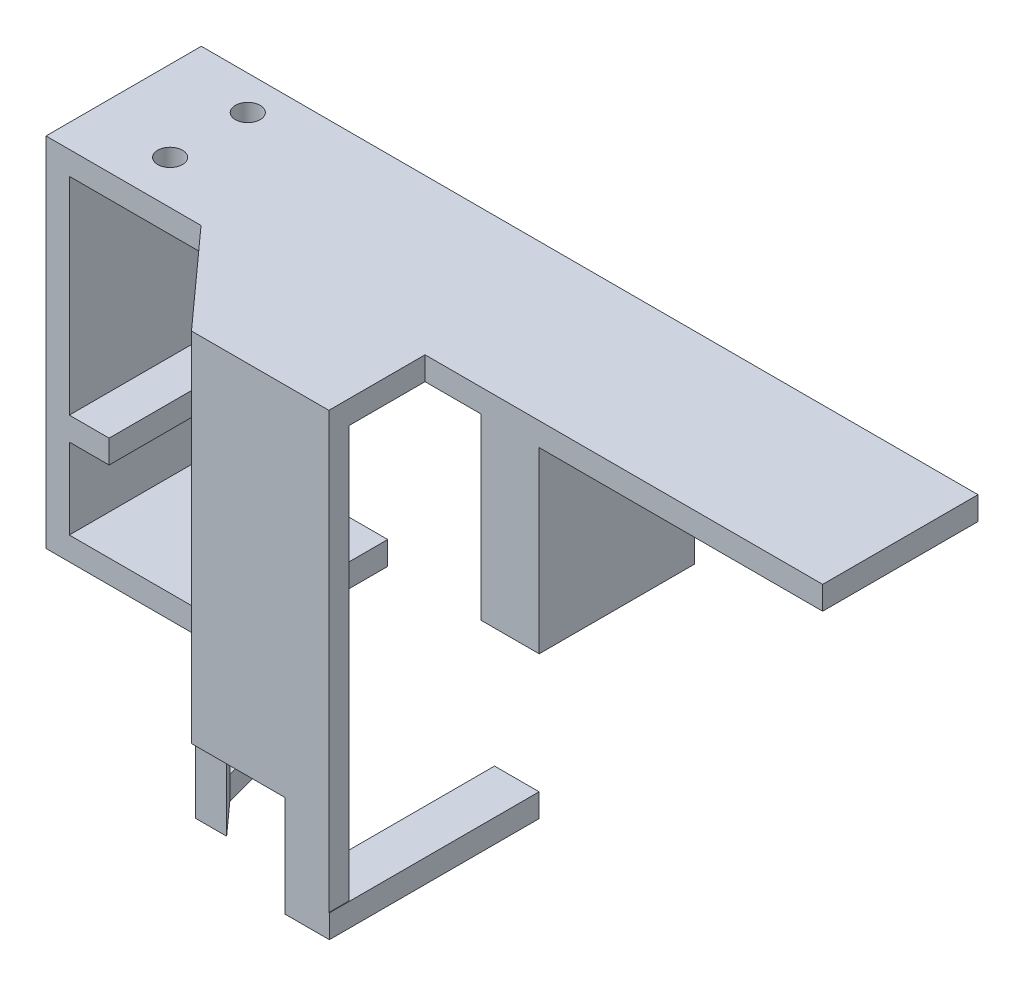
SolidWorks part; units mm, degrees
ref_plane "Front" through (0, 0, 0) normal (0, 0, 1) x (1, 0, 0)
ref_plane "Top" through (0, 0, 0) normal (0, 1, 0) x (1, 0, 0)
ref_plane "Right" through (0, 0, 0) normal (1, 0, 0) x (0, 0, -1)
sketch "Sketch1" plane through (0, 0, 0) normal (0, 1, 0) x (1, 0, 0)
  line L1 (0, 0) -> (100, 0)
  line L2 (0, 0) -> (0, 20)
  line L3 (0, 20) -> (100, 20)
  line L4 (100, 0) -> (100, 20)
  dimension "D1" = 100
  dimension "D2" = 20
extrude "Boss-Extrude1" add sketch "Sketch1" along normal blind 3
sketch "Sketch4" plane through (0, 0, -20) normal (0, 0, -1) x (-1, 0, 0)
  line L1 (0, 0) -> (-3, 0)
  line L2 (0, 0) -> (0, -43)
  line L3 (0, -43) -> (-3, -43)
  line L4 (-3, 0) -> (-3, -43)
  line L6 (-3, -24) -> (-3, -26.6921)
  line M5 (-100, 0) -> (0, 0)
  dimension "D1" = 43
  dimension "D4" = 3
extrude "Boss-Extrude3" add sketch "Sketch4" against normal blind 20 contours L4 L3 L2 M5 | L4 region at (1.5, -21.5, -20)
sketch "Sketch8" plane through (0, 0, -20) normal (0, 0, -1) x (-1, 0, 0)
  line L0 (0, 3) -> (0, -43) construction
  line L1 (-24, -40) -> (0, -40)
  line L2 (-24, -40) -> (-24, -43)
  line L3 (-24, -43) -> (0, -43)
  line L4 (0, -40) -> (0, -43)
  line L5 (0, -43) -> (-3, -43) construction
  dimension "D1" = 24
  dimension "D2" = 0
  dimension "D3" = 0
  dimension "D4" = 3
extrude "Boss-Extrude6" add sketch "Sketch8" against normal blind 20
sketch "Sketch10" plane through (0, 0, 0) normal (0, 0, 1) x (1, 0, 0)
  line L0 (3, -40) -> (24, -40) construction
  line L1 (2.1265, -29.63) -> (8.1265, -29.63)
  line L2 (2.1265, -29.63) -> (2.1265, -26.63)
  line L3 (2.1265, -26.63) -> (8.1265, -26.63)
  line L4 (8.1265, -29.63) -> (8.1265, -26.63)
  dimension "D1" = 10.37
  dimension "D2" = 3
  dimension "D3" = 6
extrude "Boss-Extrude9" add sketch "Sketch10" against normal blind 20
sketch "Sketch11" plane through (0, -43, 0) normal (0, -1, 0) x (1, 0, 0)
  circle A0 centre (20.8527, -10.1658) radius 1.5
sketch "Sketch12" plane through (0, -43, 0) normal (0, -1, 0) x (-1, 0, 0)
  line L0 (0, 0) -> (0, 20) construction
  line L1 (0, 0) -> (-24, 0) construction
  circle A0 centre (-10.38, 5.6) radius 1.6
  circle A1 centre (-10.38, 15.6) radius 1.6
  dimension "D2" = 5.6
  dimension "D3" = 10
  dimension "D1" = 10.38
extrude "Cut-Extrude1" cut sketch "Sketch12" against normal blind 80
extrude "Cut-Extrude2" cut sketch "Sketch11" against normal blind 20 contours A0
sketch "Sketch13" plane through (0, -43, 0) normal (0, -1, 0) x (1, 0, 0)
  line L1 (5.0707, -18.7755) -> (13.032, -18.7755)
  line L2 (5.0707, -18.7755) -> (5.0707, -3.4745)
  line L3 (5.0707, -3.4745) -> (13.032, -3.4745)
  line L4 (13.032, -18.7755) -> (13.032, -3.4745)
extrude "Boss-Extrude10" add sketch "Sketch13" against normal blind 3
sketch "Sketch14" plane through (0, 0, 0) normal (0, -1, 0) x (-1, 0, 0)
  line L0 (-3, 0) -> (-100, 0) construction
  line L1 (-63.4991, 0) -> (-56.0346, 0)
  line L2 (-63.4991, 0) -> (-63.4991, 20)
  line L3 (-63.4991, 20) -> (-56.0346, 20)
  line L4 (-56.0346, 0) -> (-56.0346, 20)
  line L5 (-100, 20) -> (-3, 20) construction
extrude "Boss-Extrude13" add sketch "Sketch14" along normal blind 23
sketch "Sketch18" plane through (0, -43, 0) normal (0, -1, 0) x (1, 0, 0)
  line L0 (24, 0) -> (32.8053, 9.7793)
  line L1 (32.8053, 9.7793) -> (48.8053, 9.7793)
  line L2 (48.8053, 9.7793) -> (48.8053, 12.3849)
  line L3 (48.8053, 12.3849) -> (31.1145, 12.3849)
  line L4 (31.1145, 12.3849) -> (19.9631, 0)
  line L5 (0, 0) -> (24, 0) construction
  line L6 (19.9631, 0) -> (24, 0)
  dimension "D1" = 132
  dimension "D2" = 3
  dimension "D3" = 16
extrude "Boss-Extrude15" add sketch "Sketch18" against normal blind 46
sketch "Sketch19" plane through (0, 3, 0) normal (0, 1, 0) x (1, 0, 0)
  line L0 (24, 0) -> (32.8053, -9.7793)
  line L1 (32.8053, -9.7793) -> (48.8053, -9.7793)
  line L2 (48.8053, -9.7793) -> (48.8053, 0.6164)
  line L3 (48.8053, 0.6164) -> (24, 0)
extrude "Boss-Extrude16" add sketch "Sketch19" against normal blind 3
sketch "Sketch23" plane through (0, -43, 0) normal (0, -1, 0) x (-1, 0, 0)
  line L0 (-32.8053, -9.7793) -> (-48.8053, -9.7793) construction
  line L1 (-48.8053, -12.3849) -> (-43.1369, -12.3849)
  line L2 (-48.8053, -12.3849) -> (-48.8053, -9.7793)
  line L3 (-48.8053, -9.7793) -> (-43.1369, -9.7793)
  line L4 (-43.1369, -12.3849) -> (-43.1369, -9.7793)
  line L5 (-26.6819, -7.4619) -> (-24.9881, -3.3815)
  line L6 (-31.1145, -12.3849) -> (-19.9631, 0) construction
  line L7 (-24.9881, -3.3815) -> (-27.0447, -3.3815)
  line L8 (-24, 0) -> (-32.8053, -9.7793) construction
  line L9 (-27.0447, -3.3815) -> (-30.7188, -7.4619)
  line L10 (-30.7188, -7.4619) -> (-26.6819, -7.4619)
extrude "Boss-Extrude17" add sketch "Sketch23" along normal blind 10
sketch "Sketch24" plane through (0, -53, 0) normal (0, -1, 0) x (1, 0, 0)
  line L0 (26.6819, 7.4619) -> (24.3552, 1.8567)
  line L1 (43.1369, 12.3849) -> (48.8731, 12.3849)
  line L2 (43.1369, 12.3849) -> (43.1369, -14.6151)
  line L3 (43.1369, -14.6151) -> (48.8731, -14.6151)
  line L4 (48.8731, 12.3849) -> (48.8731, -14.6151)
  line L5 (26.6819, 7.4619) -> (24.9881, 3.3815) construction
  line L6 (24.3552, 1.8567) -> (18.2213, -12.9208)
  line L7 (18.2213, -12.9208) -> (22.622, -12.9208)
  line L8 (22.622, -12.9208) -> (27.0447, 3.3815)
  line L9 (27.0447, 3.3815) -> (30.7188, 7.4619)
  line L10 (30.7188, 7.4619) -> (26.6819, 7.4619)
  dimension "D1" = 27
extrude "Boss-Extrude18" add sketch "Sketch24" along normal blind 3
